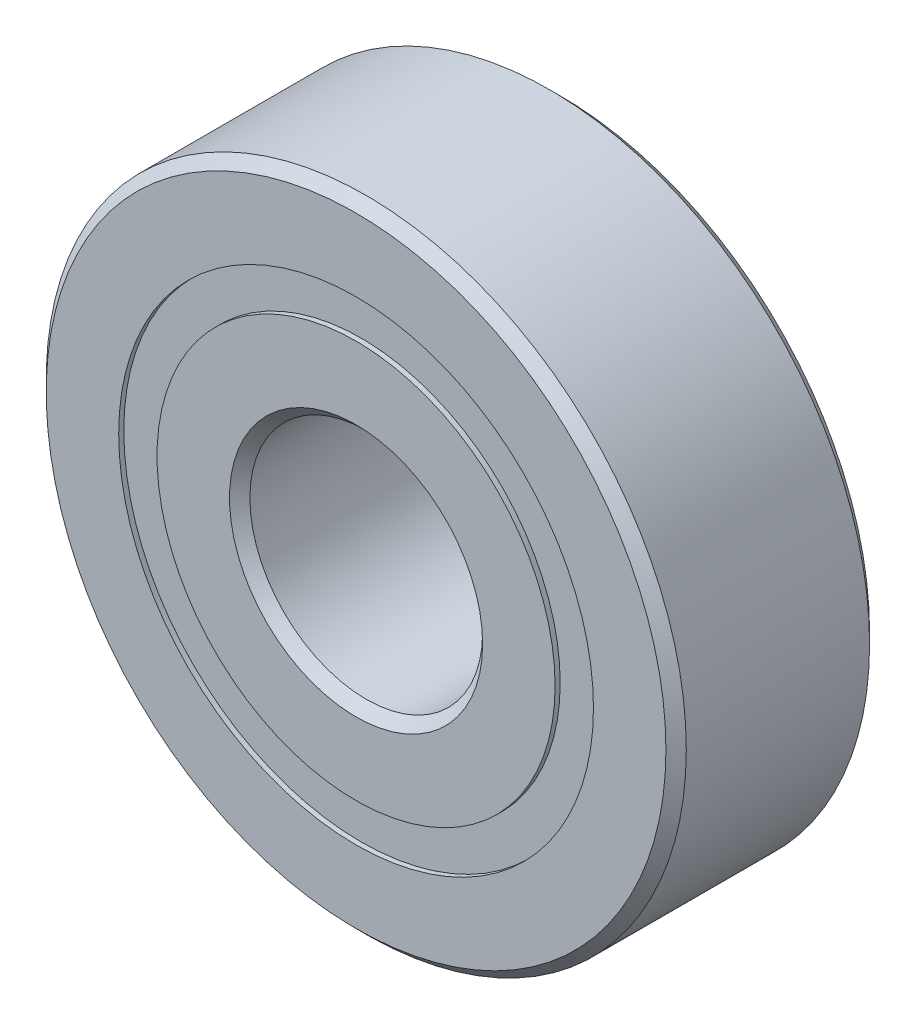
SolidWorks part; units mm, degrees
ref_plane "Front Plane" through (0, 0, 0) normal (0, 0, 1) x (1, 0, 0)
ref_plane "Top Plane" through (0, 0, 0) normal (0, 1, 0) x (1, 0, 0)
ref_plane "Right Plane" through (0, 0, 0) normal (1, 0, 0) x (0, 0, -1)
sketch "Sketch1" plane through (0, 0, 0) normal (0, 0, 1) x (1, 0, 0)
  circle A0 centre (0, 0) radius 11 construction
  circle A1 centre (0, 0) radius 4 construction
  dimension "OD" = 22
  dimension "Shaft Dia" = 8
sketch "Sketch2" plane through (0, 0, 0) normal (1, 0, 0) x (0, 0, -1)
  line L0 (-3.5, 0) -> (3.5, 0) construction
  line L1 (0, 11) -> (0, -11) construction
  line L2 (3.15, 11) -> (-3.15, 11) construction
  line L3 (-3.15, 11) -> (-3.5, 10.65) construction
  line L4 (-3.5, 10.65) -> (-3.5, 8.1593) construction
  line L5 (-3.5, 8.1593) -> (-1.5556, 8.1593) construction
  line L6 (3.5, 8.1593) -> (1.5556, 8.1593) construction
  line L7 (3.5, 10.65) -> (3.5, 8.1593) construction
  line L8 (3.15, 11) -> (3.5, 10.65) construction
  line L9 (0, 11) -> (0, 7.5) construction
  line L10 (0, 7.5) -> (0, 4) construction
  line L11 (3.5, 7.5) -> (-3.5, 7.5) construction
  line L12 (-3.5, 4.35) -> (-3.5, 6.8407) construction
  line L13 (-3.15, 4) -> (-3.5, 4.35) construction
  line L14 (3.15, 4) -> (-3.15, 4) construction
  line L15 (3.15, 4) -> (3.5, 4.35) construction
  line L16 (3.5, 4.35) -> (3.5, 6.8407) construction
  line L17 (3.5, 6.8407) -> (1.5556, 6.8407) construction
  line L18 (-3.5, 6.8407) -> (-1.5556, 6.8407) construction
  arc A0 (-1.5556, 8.1593) -> (1.5556, 8.1593) centre (0, 7.5) cw construction
  arc A1 (-1.5556, 6.8407) -> (1.5556, 6.8407) centre (0, 7.5) ccw construction
  point P14 (0, 4)
  point P18 (0, 7.5)
  dimension "D1" = 45
  dimension "D2" = 0.35
  dimension "D3" = 3.1111
  dimension "D4" = 0.6593
  dimension "Width" = 7
sketch "Sketch6" plane through (0, 0, 0) normal (1, 0, 0) x (0, 0, -1)
  line L0 (-3.5, 10.65) -> (-3.5, 8.1593) construction
  line L1 (-3.15, 11) -> (-3.5, 10.65) construction
  line L2 (3.15, 11) -> (-3.15, 11) construction
  line L3 (3.15, 11) -> (3.5, 10.65) construction
  line L4 (3.5, 10.65) -> (3.5, 8.1593) construction
  line L5 (3.5, 8.1593) -> (1.5556, 8.1593) construction
  line L6 (-3.5, 8.1593) -> (-1.5556, 8.1593) construction
  line L7 (-3.5, 10.65) -> (-3.5, 8.1593)
  line L8 (-3.15, 11) -> (-3.5, 10.65)
  line L9 (3.15, 11) -> (-3.15, 11)
  line L10 (3.15, 11) -> (3.5, 10.65)
  line L11 (3.5, 10.65) -> (3.5, 8.1593)
  line L12 (3.5, 8.1593) -> (1.5556, 8.1593)
  line L13 (-3.5, 8.1593) -> (-1.5556, 8.1593)
  line L14 (-3.5, 4.35) -> (-3.5, 6.8407) construction
  line L15 (-3.15, 4) -> (-3.5, 4.35) construction
  line L16 (3.15, 4) -> (-3.15, 4) construction
  line L17 (3.15, 4) -> (3.5, 4.35) construction
  line L18 (3.5, 4.35) -> (3.5, 6.8407) construction
  line L19 (3.5, 6.8407) -> (1.5556, 6.8407) construction
  line L20 (-3.5, 6.8407) -> (-1.5556, 6.8407) construction
  line L21 (-3.5, 4.35) -> (-3.5, 6.8407)
  line L22 (-3.15, 4) -> (-3.5, 4.35)
  line L23 (3.15, 4) -> (-3.15, 4)
  line L24 (3.15, 4) -> (3.5, 4.35)
  line L25 (3.5, 4.35) -> (3.5, 6.8407)
  line L26 (3.5, 6.8407) -> (1.5556, 6.8407)
  line L27 (-3.5, 6.8407) -> (-1.5556, 6.8407)
  arc A0 (1.5556, 8.1593) -> (-1.5556, 8.1593) centre (0, 7.5) ccw construction
  arc A1 (1.5556, 8.1593) -> (-1.5556, 8.1593) centre (0, 7.5) ccw
  arc A2 (-1.5556, 6.8407) -> (1.5556, 6.8407) centre (0, 7.5) ccw construction
  arc A3 (-1.5556, 6.8407) -> (1.5556, 6.8407) centre (0, 7.5) ccw
revolve "Revolve1" add sketch "Sketch6" angle 360 about L0
sketch "Sketch4" plane through (0, 0, 0) normal (1, 0, 0) x (0, 0, -1)
  line L0 (-1.6895, 7.5) -> (1.6895, 7.5)
  arc A2 (-1.6895, 7.5) -> (1.6895, 7.5) centre (0, 7.5) cw
  arc A3 (1.5556, 8.1593) -> (-1.5556, 8.1593) centre (0, 7.5) ccw construction
revolve "Revolve2" add sketch "Sketch4" angle 360 about L0
ref_axis "Axis1" through (0, 0, -3.5) along (0, 0, 1)
pattern_circular "CirPattern1" count 12 every 30 about axis through (0, 0, -3.5) along (0, 0, 1) of bodies 104
sketch "Sketch5" plane through (0, 0, 0) normal (1, 0, 0) x (0, 0, -1)
  line L0 (-3.5, 8.1593) -> (-1.5556, 8.1593) construction
  line L1 (-3.325, 8.1593) -> (-1.6895, 8.1593)
  line L2 (-3.325, 8.1593) -> (-3.325, 6.8407)
  line L3 (-3.325, 6.8407) -> (-1.6895, 6.8407)
  line L4 (-1.6895, 8.1593) -> (-1.6895, 6.8407)
  line L6 (3.5, 8.1593) -> (1.5556, 8.1593) construction
  line L7 (3.325, 8.1593) -> (1.6895, 8.1593)
  line L8 (3.325, 8.1593) -> (3.325, 6.8407)
  line L9 (3.325, 6.8407) -> (1.6895, 6.8407)
  line L10 (1.6895, 8.1593) -> (1.6895, 6.8407)
  line L12 (-3.15, 11) -> (-3.5, 10.65) construction
  line L13 (-3.5, 6.8407) -> (-1.5556, 6.8407) construction
  line L14 (3.5, 6.8407) -> (1.5556, 6.8407) construction
  point P18 (-3.325, 10.825)
revolve "Revolve3" add sketch "Sketch5" angle 360 about L0
equation "\"D2@Sketch2\"= \"Width@Sketch2\" * .05"
equation "\"D3@Sketch2\"=\"Width@Sketch2\" / 2.25"
equation "\"D4@Sketch2\"= ( ( ( \"OD@Sketch1\" - \"Width@Sketch2\" ) / 2 ) / 3.25 ) / 3.5"
equation "\"D2@CirPattern1\" = 360/\"Balls@CirPattern1\""
